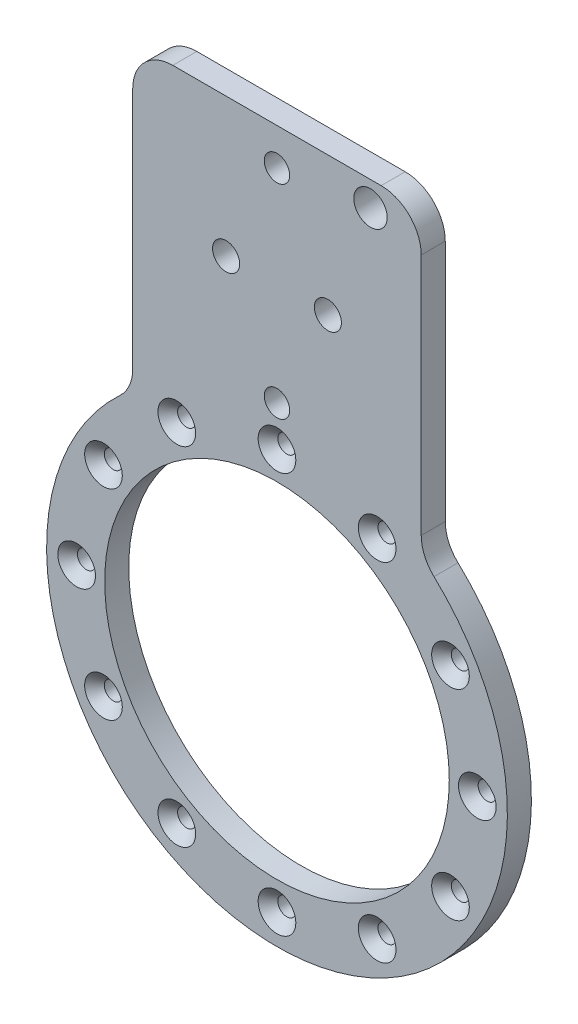
SolidWorks part; units mm, degrees
note: '?' marks a value the reader was unsure of.
material "6061-T6 (SS)"
ref_plane "Front Plane" through (0, 0, 0) normal (0, 0, 1) x (1, 0, 0)
ref_plane "Top Plane" through (0, 0, 0) normal (0, 1, 0) x (1, 0, 0)
ref_plane "Right Plane" through (0, 0, 0) normal (1, 0, 0) x (0, 0, -1)
sketch "Sketch1" plane through (0, 0, 0) normal (0, 0, 1) x (1, 0, 0)
  line L0 (-36, 44.8358) -> (-36, 120)
  line L1 (-36, 120) -> (36, 120)
  line L2 (36, 120) -> (36, 44.8358)
  circle A0 centre (0, 0) radius 43
  circle A1 centre (0, 0) radius 50 construction
  arc A2 (-36, 44.8358) -> (36, 44.8358) centre (0, 0) ccw
  point P7 (0, 120)
  dimension "D2" = 115
  dimension "D3" = 100
  dimension "D4" = 86
  dimension "D1" = 120
  dimension "D5" = 72
extrude "base" add sketch "Sketch1" along normal mid plane 6
hole_wizard "M4 Clearance Hole1" positions "Sketch3" profile "Sketch4" hole size "M4" standard "ISO" end condition through all
sketch "Sketch3" plane through (0, 0, 3) normal (0, 0, 1) x (1, 0, 0)
  point P0 (0, 50)
  point P16 (25, 43.3013)
  point P17 (43.3013, 25)
  point P18 (50, 0)
  point P19 (43.3013, -25)
  point P20 (25, -43.3013)
  point P21 (0, -50)
  point P22 (-25, -43.3013)
  point P23 (-43.3013, -25)
  point P24 (-50, 0)
  point P25 (-43.3013, 25)
  point P26 (-25, 43.3013)
  dimension "D1" = 50
  dimension "D3" = 50
  dimension "D2" = 12
sketch "Sketch4" plane through (0, 50, 3) normal (1, 0, 0) x (0, -1, 0)
  line L0 (0, 0) -> (0, 6)
  line L1 (0, 6) -> (2.25, 6)
  line L2 (2.25, 6) -> (2.25, 0)
  line L5 (2.25, 0) -> (0, 0)
  line L11 (0, -6.35) -> (0, 107.95) construction
  dimension "Thru Hole Dia." = 4.5
  dimension "Thru Hole Depth" = 6
hole_wizard "M4 Clearance Hole2" positions "Sketch5" profile "Sketch6" hole size "M4" standard "ISO" end condition through all
sketch "Sketch5" plane through (0, 0, 3) normal (0, 0, 1) x (1, 0, 0)
  point P0 (0, 60)
  point P2 (0, 110.8)
  dimension "D1" = 60
  dimension "D2" = 50.8
sketch "Sketch6" plane through (0, 60, 3) normal (1, 0, 0) x (0, -1, 0)
  line L0 (0, 0) -> (0, 6)
  line L1 (0, 6) -> (3.175, 6)
  line L2 (3.175, 6) -> (3.175, 0)
  line L5 (3.175, 0) -> (0, 0)
  line L11 (0, -6.35) -> (0, 107.95) construction
  dimension "Thru Hole Dia." = 6.35
  dimension "Thru Hole Depth" = 6
hole_wizard "1/4 Clearance Hole1" positions "Sketch7" profile "Sketch8" hole size "1/4" standard "ANSI Inch" end condition through all
sketch "Sketch7" plane through (0, 0, 3) normal (0, 0, 1) x (1, 0, 0)
  circle A0 centre (0, 110.8) radius 3.175 construction
  point P0 (-12.7, 85.4)
  point P2 (12.7, 85.4)
  dimension "D3" = 25.4
  dimension "D1" = 25.4
  dimension "D2" = 12.7
sketch "Sketch8" plane through (-12.7, 85.4, 3) normal (1, 0, 0) x (0, -1, 0)
  line L0 (0, 0) -> (0, 6)
  line L1 (0, 6) -> (3.3782, 6)
  line L2 (3.3782, 6) -> (3.3782, 0)
  line L5 (3.3782, 0) -> (0, 0)
  line L11 (0, -6.35) -> (0, 107.95) construction
  dimension "Thru Hole Dia." = 6.7564
  dimension "Thru Hole Depth" = 6
fillet "Fillet1" radius 10 4 edges at (36, 120, 0) (-36, 120, 0) (-36, 44.8358, 0) (36, 44.8358, 0)
sketch "Sketch9" plane through (0, 0, 3) normal (0, 0, 1) x (1, 0, 0)
  line L0 (57.5, 0) -> (63.85, 0)
  line L1 (49, -30.0874) -> (51.6912, -37.4813)
  arc A0 (49, -30.0874) -> (57.5, 0) centre (0, 0) ccw
  arc A1 (-39.1852, 42.0805) -> (39.1852, 42.0805) centre (0, 0) ccw construction
  arc A2 (63.85, 0) -> (51.6912, -37.4813) centre (0, 0) cw
  dimension "D1" = 20
  dimension "D2" = 6.35
  dimension "D3" = 8.5
extrude "stoper" [suppressed] add sketch "Sketch9" along normal blind 20 and the other way up to surface
ref_axis "Axis1" through (0, 0, 3) along (0, 0, -1)?
sketch "Sketch10" plane through (0, 0, 3) normal (0, 0, 1) x (1, 0, 0)
  line L0 (0, 0) -> (0, 43) construction
  circle A0 centre (0, 0) radius 43 construction
hole_wizard "CSK for M4 Flat Head Machine Screw1" positions "Sketch11" profile "Sketch12" countersink size "M4" standard "ANSI Metric" end condition through all
sketch "Sketch11" plane through (0, 0, 3) normal (0, 0, 1) x (1, 0, 0)
  point P0 (0, 50)
  point P4 (25, 43.3013)
  point P7 (43.3013, 25)
  point P10 (50, 0)
  point P13 (43.3013, -25)
  point P16 (25, -43.3013)
  point P19 (0, -50)
  point P22 (-25, -43.3013)
  point P25 (-43.3013, -25)
  point P28 (-50, 0)
  point P31 (-43.3013, 25)
  point P34 (-25, 43.3013)
sketch "Sketch12" plane through (0, 50, 3) normal (1, 0, 0) x (0, -1, 0)
  line L0 (0, 0) -> (0, 6)
  line L1 (0, 6) -> (2.25, 6)
  line L2 (2.25, 6) -> (2.25, 2.45)
  line L3 (2.25, 2.45) -> (4.7, 0)
  line L5 (4.7, 0) -> (0, 0)
  line L6 (-2.25, 2.45) -> (-4.7, 0) construction
  line L11 (0, -6.35) -> (0, 107.95) construction
  dimension "Thru Hole Dia." = 4.5
  dimension "Thru Hole Depth" = 6
  dimension "Near C'Sink Dia." = 9.4
  dimension "Near C'Sink Angle" = 90
sketch "Sketch15" plane through (0, 0, -3) normal (0, 0, -1) x (-1, 0, 0)
  line L0 (-26, 120) -> (26, 120) construction
  line L1 (-36, 49.3989) -> (-36, 110) construction
  circle A0 centre (-23.335, 113.835) radius 4.165
  dimension "D1" = 8.33
  dimension "D2" = 6.165
  dimension "D3" = 12.665
extrude "Cut-Extrude1" cut sketch "Sketch15" against normal through all contours A0
hole_wizard "1/4 (0.25) Diameter Hole1" [suppressed] positions "Sketch13" profile "Sketch14" hole size "1/4" standard "ANSI Inch"
sketch "Sketch13" plane through (0, 0, -3) normal (0, 0, -1) x (-1, 0, 0)
  line L4 (-36, 49.3989) -> (-36, 110) construction
  line L5 (36, 110) -> (36, 49.3989) construction
  point P0 (-23.3, 110.8)
  point P3 (23.3, 110.8)
  dimension "D1" = 12.7
  dimension "D2" = 12.7
sketch "Sketch14" plane through (23.3, 110.8, -3) normal (1, 0, 0) x (0, 1, 0)
  line L0 (0, 0) -> (0, 6)
  line L1 (0, 6) -> (4.1656, 6)
  line L2 (4.1656, 6) -> (4.1656, 0)
  line L5 (4.1656, 0) -> (0, 0)
  line L11 (0, -6.35) -> (0, 107.95) construction
  dimension "Thru Hole Dia." = 8.3312
  dimension "Thru Hole Depth" = 6
